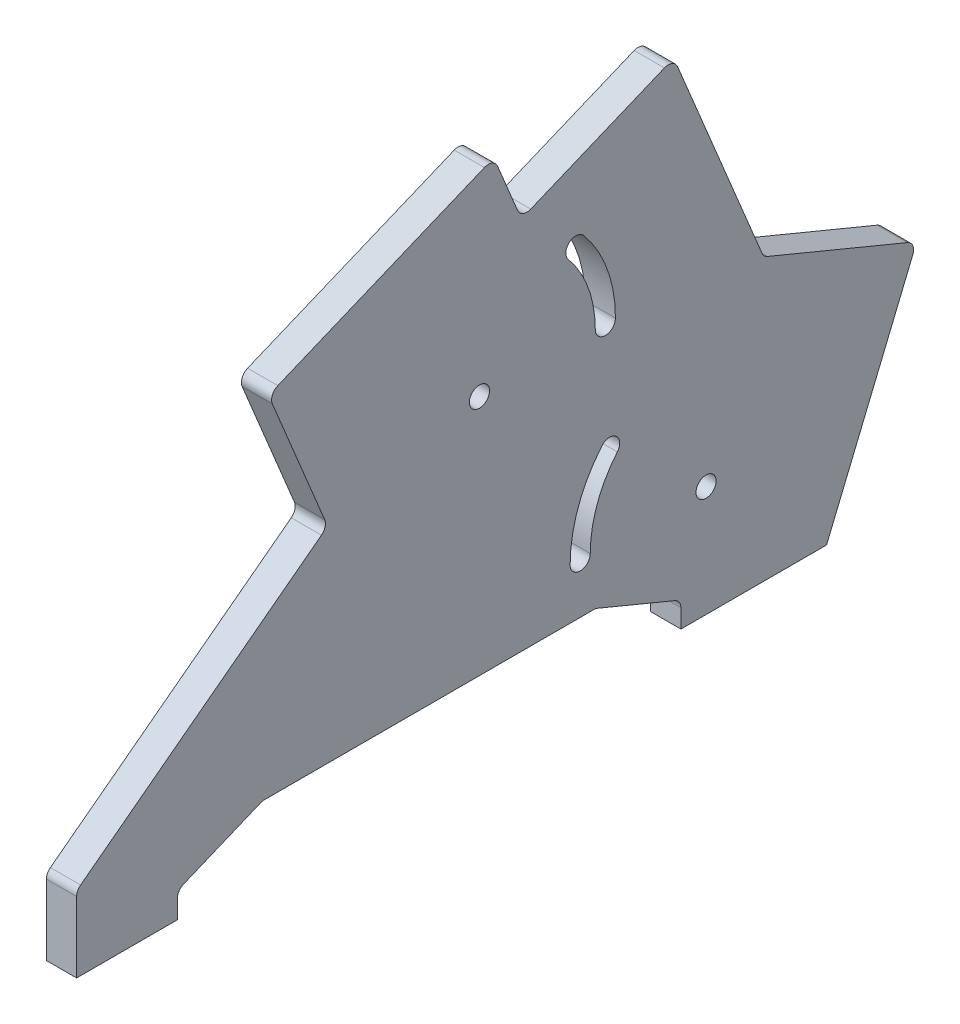
SolidWorks part; units mm, degrees
material "PMMA"
ref_plane "Front Plane" through (0, 0, 0) normal (0, 0, 1) x (1, 0, 0)
ref_plane "Top Plane" through (0, 0, 0) normal (0, 1, 0) x (1, 0, 0)
ref_plane "Right Plane" through (0, 0, 0) normal (1, 0, 0) x (0, 0, -1)
sketch "Sketch1" plane through (0, 0, 0) normal (1, 0, 0) x (0, 0, -1)
  line L0 (0, 0) -> (0, 15)
  line L1 (38.8897, 80.8553) -> (54.5797, 42.9762) construction
  line L2 (38.8897, 80.8553) -> (112.8001, 111.47) construction
  line L3 (54.5797, 42.9762) -> (128.4901, 73.5909) construction
  line L5 (112.8001, 111.47) -> (128.4901, 73.5909) construction
  line L6 (20, 5) -> (20, 0)
  line L7 (0, 0) -> (20, 0)
  line L10 (80, 60) -> (105, 60) construction
  line L11 (99.1511, 76.0697) -> (80, 60) construction
  line L12 (100, 22) -> (125, 22) construction
  line L13 (125, 22) -> (105.8489, 38.0697) construction
  line L14 (166.1103, 42.8553) -> (150.4203, 4.9762) construction
  line L15 (166.1103, 42.8553) -> (92.1999, 73.47) construction
  line L16 (150.4203, 4.9762) -> (76.5099, 35.5909) construction
  line L17 (92.1999, 73.47) -> (76.5099, 35.5909) construction
  line L19 (166.8247, 43.2195) -> (136.4285, 55.81)
  line L20 (38.1102, 81.1261) -> (82.8344, 99.6514)
  line L21 (82.8344, 99.6514) -> (88.3305, 86.3826)
  line L22 (38.1102, 81.1261) -> (49.8545, 52.7728)
  line L23 (49.8545, 52.7728) -> (0, 15)
  line L24 (88.3305, 86.3826) -> (118.5757, 98.9106)
  line L25 (118.5757, 98.9106) -> (136.4285, 55.81)
  line L43 (148.9226, 0) -> (120, 0)
  line L56 (120, 5) -> (120, 0)
  line L58 (20, 5) -> (36.8995, 12)
  line L59 (36.8995, 12) -> (103.1005, 12)
  line L60 (103.1005, 12) -> (120, 5)
  line L61 (148.9226, 0) -> (166.8247, 43.2195)
  line L63 (174.6584, 100) -> (-14.1241, 100) construction
  circle A0 centre (80, 60) radius 2
  circle A1 centre (125, 22) radius 2
  arc A2 (99.1511, 76.0697) -> (105, 60) centre (80, 60) cw construction
  arc A3 (107, 60) -> (100.6832, 77.3553) centre (80, 60) ccw
  arc A4 (103, 60) -> (97.619, 74.7841) centre (80, 60) ccw
  arc A5 (103, 60) -> (107, 60) centre (105, 60) ccw
  arc A6 (100.6832, 77.3553) -> (97.619, 74.7841) centre (99.1511, 76.0697) ccw
  arc A7 (105.8489, 38.0697) -> (100, 22) centre (125, 22) ccw construction
  arc A8 (104.3168, 39.3553) -> (98, 22) centre (125, 22) ccw
  arc A9 (107.381, 36.7841) -> (102, 22) centre (125, 22) ccw
  arc A10 (107.381, 36.7841) -> (104.3168, 39.3553) centre (105.8489, 38.0697) ccw
  arc A11 (98, 22) -> (102, 22) centre (100, 22) ccw
  point P17 (103.4923, 68.5505)
  point P22 (101.5077, 30.5505)
  dimension "D1" = 4
  dimension "D3" = 2
  dimension "D8" = 15
  dimension "D11" = 22
  dimension "D12" = 80
  dimension "D14" = 10
  dimension "D17" = 6
  dimension "D21" = 30
  dimension "D22" = 35
  dimension "D23" = 80
  dimension "D18" = 6
  dimension "D29" = 60
  dimension "D2" = 25
  dimension "D4" = 25
  dimension "D5" = 40
  dimension "D6" = 40
  dimension "D7" = 125
  dimension "D9" = 20
  dimension "D10" = 100
  dimension "D13" = 5
  dimension "D20" = 30
  dimension "D31" = 22.5
  dimension "D32" = 100
  dimension "D33" = 22.5
extrude "Boss-Extrude1" add sketch "Sketch1" along normal blind 6
fillet "Fillet1" radius 2 12 edges at (3, 12, -36.8995) (3, 5, -20) (3, 12, -103.1005) (3, 43.2195, -166.8247) (3, 55.81, -136.4285) (3, 98.9106, -118.5757) (3, 86.3826, -88.3305) (3, 99.6514, -82.8344) (3, 81.1261, -38.1102) (3, 52.7728, -49.8545) (3, 15, 0) (3, 5, -120)
hole_wizard "Tap Drill for M3 Tap1" positions "Sketch3" profile "Sketch2" hole size "M3" standard "ISO"
sketch "Sketch3" plane through (0, 0, 0) normal (0, -1, 0) x (-1, 0, 0)
  line L0 (-6, 20) -> (0, 20) construction
  line L1 (0, 0) -> (0, 20) construction
  line L2 (-6, 120) -> (0, 120) construction
  point P0 (-3, 10)
  point P2 (-3, 130)
  dimension "D1" = 10
  dimension "D2" = 3
  dimension "D3" = 10
sketch "Sketch2" plane through (3, 0, -10) normal (1, 0, 0) x (0, 0, -1)
  line L0 (0, 0) -> (0, 10.7511)
  line L1 (0, 10.7511) -> (1.25, 10)
  line L2 (1.25, 10) -> (1.25, 0)
  line L5 (1.25, 0) -> (0, 0)
  line L10 (0, 10.7511) -> (-1.25, 10) construction
  line L11 (0, -6.35) -> (0, 107.95) construction
  dimension "Hole Dia." = 2.5
  dimension "Hole Depth" = 10
  dimension "Drill Angle" = 118
equation "\"ˇ35\"=76.24"
